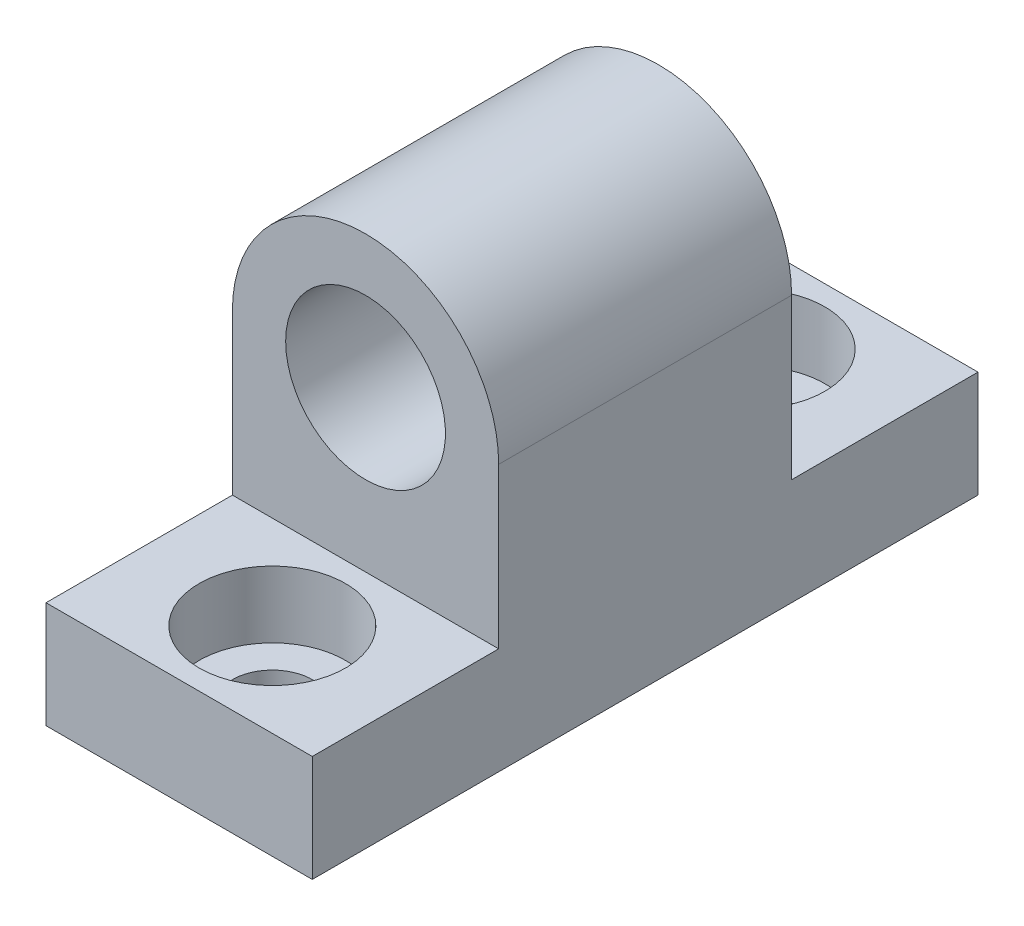
SolidWorks part; units mm, degrees
material "Легированная сталь (SS)"
ref_plane "Спереди" through (0, 0, 0) normal (0, 0, 1) x (1, 0, 0)
ref_plane "Сверху" through (0, 0, 0) normal (0, 1, 0) x (1, 0, 0)
ref_plane "Справа" through (0, 0, 0) normal (1, 0, 0) x (0, 0, -1)
sketch "Эскиз1" plane through (0, 0, 0) normal (0, 0, 1) x (1, 0, 0)
  line L1 (-10, 0) -> (10, 0)
  line L2 (-10, 0) -> (-10, 20)
  line L4 (10, 0) -> (10, 20)
  arc A0 (10, 20) -> (-10, 20) centre (0, 20) ccw
  circle A1 centre (0, 20) radius 6
  dimension "D2" = 30
  dimension "D3" = 12
  dimension "D1" = 20
extrude "Бобышка-Вытянуть1" add sketch "Эскиз1" along normal mid plane 50
sketch "Эскиз2" plane through (0, 0, 0) normal (1, 0, 0) x (0, 0, -1)
  line L0 (-25, 0) -> (25, 0) construction
  line L1 (32.9029, 8) -> (11, 8)
  line L2 (32.9029, 8) -> (32.9029, 39.1917)
  line L3 (32.9029, 39.1917) -> (11, 39.1917)
  line L4 (11, 8) -> (11, 39.1917)
  line L5 (-34.5139, 8) -> (-11, 8)
  line L6 (-34.5139, 8) -> (-34.5139, 41.7756)
  line L7 (-34.5139, 41.7756) -> (-11, 41.7756)
  line L8 (-11, 8) -> (-11, 41.7756)
  line L9 (0, -6.0405) -> (0, 41.7756) construction
  line L10 (25, 20) -> (25, 0) construction
  dimension "D1" = 8
  dimension "D2" = 14
extrude "Вырез-Вытянуть1" cut sketch "Эскиз2" against normal through all and the other way through all
sketch "Эскиз3" plane through (-10, 0, 0) normal (-1, 0, 0) x (0, 0, 1)
  circle A0 centre (0, 20) radius 2.5
  dimension "D1" = 5
  dimension "D2" = 20
extrude "Вырез-Вытянуть2" cut sketch "Эскиз3" against normal up to next
sketch "Эскиз4" plane through (0, 0, 0) normal (0, -1, 0) x (-1, 0, 0)
  circle A0 centre (0, 0) radius 3
  dimension "D1" = 6
extrude "Вырез-Вытянуть3" cut sketch "Эскиз4" against normal blind 12
sketch "Эскиз5" plane through (0, 8, 0) normal (0, 1, 0) x (1, 0, 0)
  line L0 (0, 18) -> (0, -18) construction
  circle A0 centre (0, 18) radius 5.5
  circle A1 centre (0, -18) radius 5.5
  dimension "D1" = 11
  dimension "D2" = 36
extrude "Вырез-Вытянуть4" cut sketch "Эскиз5" against normal blind 5
sketch "Эскиз6" plane through (0, 3, 0) normal (0, 1, 0) x (1, 0, 0)
  circle A0 centre (0, 18) radius 3
  circle A1 centre (0, -18) radius 3
  circle A2 centre (0, 18) radius 5.5 construction
  dimension "D1" = 6
extrude "Вырез-Вытянуть5" cut sketch "Эскиз6" against normal through all
fillet "Скругление1" [suppressed] radius 1
ref_plane "Плоскость1" through (0, 0, 0) normal (0, 0, -1) x (-1, 0, 0)
